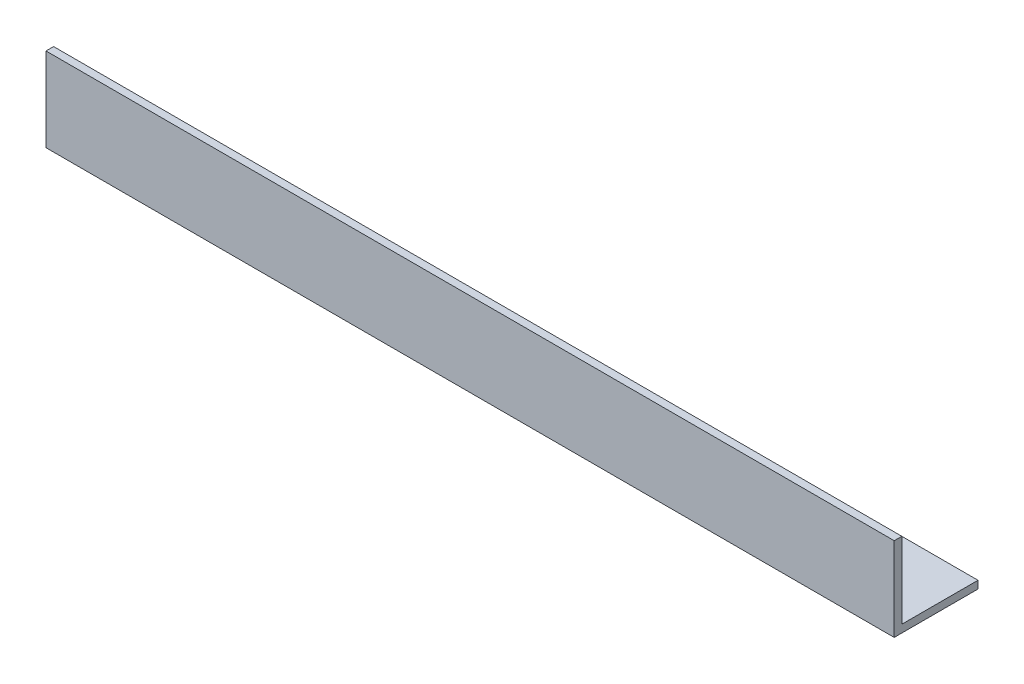
SolidWorks part; units mm, degrees
ref_plane "Спереди" through (0, 0, 0) normal (0, 0, 1) x (1, 0, 0)
ref_plane "Сверху" through (0, 0, 0) normal (0, 1, 0) x (1, 0, 0)
ref_plane "Справа" through (0, 0, 0) normal (1, 0, 0) x (0, 0, -1)
sketch "Эскиз1" plane through (0, 0, 0) normal (1, 0, 0) x (0, 0, -1)
  line L0 (0, 33) -> (0, 0)
  line L1 (0, 0) -> (33, 0)
extrude "Вытянуть-Тонкостенный1" add sketch "Эскиз1" along normal blind 334 thin thin type one direction reverse wall 3
